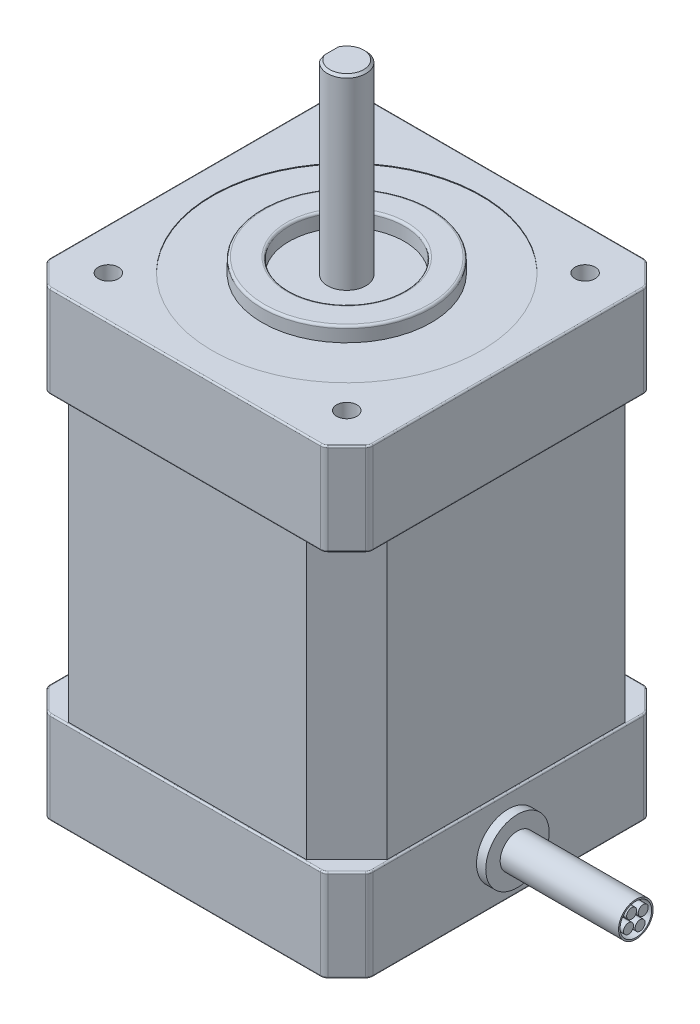
SolidWorks part; units mm, degrees
ref_plane "前视基准面" through (0, 0, 0) normal (0, 0, 1) x (1, 0, 0)
ref_plane "上视基准面" through (0, 0, 0) normal (0, 1, 0) x (1, 0, 0)
ref_plane "右视基准面" through (0, 0, 0) normal (1, 0, 0) x (0, 0, -1)
sketch "草图13" plane through (0, 0, 0) normal (0, 0, 1) x (1, 0, 0)
  line L0 (0, 0) -> (0, 60) construction
  dimension "L" = 60
sketch "草图1" plane through (0, 0, 0) normal (0, 1, 0) x (1, 0, 0)
  line L0 (0, 21) -> (0, -21) construction
  line L1 (-21, 21) -> (21, 21)
  line L2 (-21, 21) -> (-21, -21)
  line L3 (-21, -21) -> (21, -21)
  line L4 (21, 21) -> (21, -21)
  line L5 (-21, 0) -> (21, 0) construction
  dimension "D2" = 21
  dimension "W2" = 42
  dimension "D4" = 21
extrude "凸台-拉伸1" add sketch "草图1" along normal blind 60
chamfer "倒角3" distance 3 angle 45 4 edges at (21, 30, -21) (21, 30, 21) (-21, 30, 21) (-21, 30, -21)
sketch "草图2" plane through (0, 60, 0) normal (0, 1, 0) x (1, 0, 0)
  circle A0 centre (0, 0) radius 11
  dimension "E6" = 22
extrude "凸台-拉伸2" add sketch "草图2" along normal blind 1.8
ref_plane "基准面1" through (0, 12, 0) normal (0, -1, 0) x (1, 0, 0)
sketch "草图3" plane through (0, 60, 0) normal (0, 1, 0) x (1, 0, 0)
  line L0 (-2, 1.5) -> (-2, -1.5) construction
  circle A0 centre (0, 0) radius 2.5
  point P3 (2.5, 0)
  dimension "D1" = 4.5
  dimension "E4" = 5
extrude "凸台-拉伸3" add sketch "草图3" along normal blind 24
sketch "草图4" plane through (0, 12, 0) normal (0, -1, 0) x (1, 0, 0)
  line L0 (15.4716, 20.7) -> (-15.4716, 20.7)
  line L1 (-15.4716, 20.7) -> (-20.7, 15.4716)
  line L2 (-20.7, 15.4716) -> (-20.7, -15.4716)
  line L3 (-20.7, -15.4716) -> (-15.4716, -20.7)
  line L4 (-15.4716, -20.7) -> (15.4716, -20.7)
  line L5 (15.4716, -20.7) -> (20.7, -15.4716)
  line L6 (20.7, -15.4716) -> (20.7, 15.4716)
  line L7 (20.7, 15.4716) -> (15.4716, 20.7)
  line L8 (18, -21) -> (-18, -21) construction
  line L9 (-21, -18) -> (-21, 18) construction
  line L10 (21, 18) -> (21, -18) construction
  line L11 (-18, 21) -> (18, 21) construction
  line L15 (-18, 21) -> (-21, 18) construction
  line L21 (0, -21) -> (0, 21) construction
  line L22 (0, -21) -> (0, 21) construction
  line L23 (-21, 0) -> (21, 0) construction
  dimension "D1" = 0.3
  dimension "D2" = 0.3
  dimension "D3" = 0.3
  dimension "D4" = 0.3
  dimension "D5" = 2
extrude "切除-拉伸1" cut sketch "草图4" against normal blind 36 flip side to cut
fillet "圆角2" radius 1 16 edges at (21, 6, 18) (18, 6, 21) (-18, 6, 21) (-21, 6, 18) (21, 6, -18) (18, 6, -21) (-18, 6, -21) (-21, 6, -18) (-18, 54, -21) (-21, 54, -18) (21, 54, -18) (18, 54, -21) (21, 54, 18) (18, 54, 21) (-18, 54, 21) (-21, 54, 18)
fillet "圆角3" radius 0.2 64 edges at (-21, 48, 0) (-20.9239, 48, 17.9685) (0, 48, 21) (-17.9685, 48, 20.9239) (0, 12, 21) (17.9685, 12, 20.9239) (21, 12, 0) (20.9239, 12, 17.9685) (17.9685, 48, 20.9239) (21, 48, 0) (20.9239, 48, 17.9685) (-21, 12, 0) (-20.9239, 12, 17.9685) (-17.9685, 12, 20.9239) (0, 12, -21) (-17.9685, 12, -20.9239) (-20.9239, 12, -17.9685) (0, 48, -21) (-17.9685, 48, -20.9239) (-20.9239, 48, -17.9685) (-20.9239, 60, -17.9685) (-19.5, 60, -19.5) (-17.9685, 60, -20.9239) (0, 60, -21) (17.9685, 60, -20.9239) (19.5, 60, -19.5) (20.9239, 60, -17.9685) (21, 60, 0) (20.9239, 60, 17.9685) (19.5, 60, 19.5) (17.9685, 60, 20.9239) (0, 60, 21) (-17.9685, 60, 20.9239) (-20.9239, 60, 17.9685) (-20.9239, 0, -17.9685) (-21, 0, 0) (-20.9239, 0, 17.9685) (-19.5, 0, 19.5) (-17.9685, 0, 20.9239) (0, 0, 21) (17.9685, 0, 20.9239) (19.5, 0, 19.5) (20.9239, 0, 17.9685) (21, 0, 0) (20.9239, 0, -17.9685) (19.5, 0, -19.5) (17.9685, 0, -20.9239) (0, 0, -21) (-17.9685, 0, -20.9239) (-19.5, 60, 19.5) (-19.5, 48, 19.5) (19.5, 12, 19.5) (19.5, 48, 19.5) (-19.5, 12, 19.5) (-19.5, 12, -19.5) (-19.5, 48, -19.5) (-21, 60, 0) (-19.5, 0, -19.5) (17.9685, 12, -20.9239) (19.5, 12, -19.5) (20.9239, 12, -17.9685) (17.9685, 48, -20.9239) (19.5, 48, -19.5) (20.9239, 48, -17.9685)
sketch "草图14" plane through (0, 84, 0) normal (0, 1, 0) x (1, 0, 0)
  line L0 (-2, 1.5) -> (-2, -1.5) construction
  line L1 (-2, 1.5) -> (-2, -1.5)
  circle A1 centre (0, 0) radius 2.5 construction
  arc A2 (-2, 1.5) -> (-2, -1.5) centre (0, 0) ccw
extrude "切除-拉伸5" cut sketch "草图14" against normal blind 15
chamfer "倒角5" distance 0.3 angle 45 1 edges at (2.5, 84, 0)
chamfer "倒角4" distance 0.5 angle 45 1 edges at (-2, 69, 0)
chamfer "倒角6" [suppressed] distance 1 angle 45
sketch "草图6" plane through (0, 60, 0) normal (0, 1, 0) x (1, 0, 0)
  line L0 (0, 21) -> (0, -21) construction
  line L3 (-21, 0) -> (21, 0) construction
  line L7 (-21, -21) -> (21, -21) construction
  circle A0 centre (-15.5, 15.5) radius 1.3105
  circle A1 centre (15.5, 15.5) radius 1.3105
  circle A2 centre (15.5, -15.5) radius 1.3105
  circle A3 centre (-15.5, -15.5) radius 1.3105
  dimension "D1" = 31
  dimension "E2" = 2.621
  dimension "E1" = 15.5
extrude "切除-拉伸2" cut sketch "草图6" against normal blind 4.5
cosmetic thread "装饰螺纹线1" parameters "D2"=3
cosmetic thread "装饰螺纹线2" parameters "D2"=3
cosmetic thread "装饰螺纹线3" parameters "D2"=3
cosmetic thread "装饰螺纹线4" parameters "D2"=3
sketch "草图7" plane through (0, 61.8, 0) normal (0, 1, 0) x (1, 0, 0)
  circle A0 centre (0, 0) radius 7.5
  circle A1 centre (0, 0) radius 2.5
  dimension "D1" = 15
  dimension "D2" = 5
extrude "切除-拉伸3" cut sketch "草图7" against normal blind 2
sketch "草图8" plane through (21, 0, 0) normal (1, 0, 0) x (0, 0, -1)
  line L0 (0, 12) -> (0, 0) construction
  line L2 (-15.1716, 12) -> (-18, 12) construction
  circle A0 centre (0, 6) radius 4.125
  dimension "D1" = 8.25
extrude "凸台-拉伸5" add sketch "草图8" along normal blind 1.2
sketch "草图9" plane through (22.2, 0, 0) normal (1, 0, 0) x (0, 0, -1)
  circle A0 centre (0, 6) radius 2.25
  circle A1 centre (0, 6) radius 2.05
  circle A2 centre (0, 6) radius 4.125 construction
  dimension "D1" = 4.5
  dimension "D2" = 0.2
extrude "凸台-拉伸6" add sketch "草图9" along normal blind 15.4
sketch "草图10" plane through (22.2, 0, 0) normal (1, 0, 0) x (0, 0, -1)
  line L0 (0, 6) -> (-0.9526, 6.55) construction
  line L1 (0, 6) -> (0.9526, 6.55) construction
  line L2 (0, 6) -> (0, 4.9) construction
  circle A0 centre (-0.9526, 6.55) radius 0.65 construction
  circle A1 centre (0.9526, 6.55) radius 0.65
  circle A2 centre (0, 4.9) radius 0.65 construction
  circle A5 centre (0, 6) radius 1.1 construction
  dimension "D1" = 120
  dimension "D2" = 2.2
  dimension "D3" = 1.3
  dimension "D4" = 120
extrude "凸台-拉伸8" add sketch "草图10" along normal blind 15.4 contours A0 | A2 | A1
sketch "草图15" plane through (0, 60, 0) normal (0, 1, 0) x (1, 0, 0)
  circle A0 centre (0, 0) radius 17.5
  circle A1 centre (0, 0) radius 11 construction
  circle A2 centre (0, 0) radius 11
  dimension "D1" = 35
extrude "切除-拉伸6" cut sketch "草图15" against normal blind 0.1
fillet "圆角4" radius 0.3 2 edges at (0, 61.8, 7.5) (0, 61.8, 11)
pattern_circular "阵列(圆周)3" count 4 over 360 about axis through (0, 6, 0) along (1, 0, 0) of "凸台-拉伸8"
sketch "草图16" [suppressed] plane through (0, 0, -20.85) normal (0, 0, -1) x (-1, 0, 0)
  line L0 (0, 36.8) -> (0, 9.2) construction
  line L1 (15.6216, 36.8) -> (-15.6216, 36.8) construction
  line L2 (15.6216, 9.2) -> (-15.6216, 9.2) construction
  line L4 (-12.5, 7.2) -> (12.5, 7.2)
  line L5 (-12.5, 7.2) -> (-12.5, 38.8)
  line L6 (-12.5, 38.8) -> (12.5, 38.8)
  line L7 (12.5, 7.2) -> (12.5, 38.8)
  line L8 (-12.5, 7.2) -> (12.5, 38.8) construction
  line L9 (-12.5, 38.8) -> (12.5, 7.2) construction
  point P6 (0, 23)
  dimension "D1" = 2
  dimension "D2" = 25
extrude "切除-拉伸9" [suppressed] cut sketch "草图16" along normal blind 0.3
sketch "草图17" [suppressed] plane through (0, 0, 20.85) normal (0, 0, 1) x (1, 0, 0)
  line L4 (-12.5, 7.2) -> (12.5, 7.2)
  line L5 (-12.5, 38.8) -> (-12.5, 7.2)
  line L6 (12.5, 38.8) -> (-12.5, 38.8)
  line L7 (12.5, 7.2) -> (12.5, 38.8)
  line L8 (-12.5, 7.2) -> (12.5, 7.2)
  line L9 (-12.5, 38.8) -> (-12.5, 7.2)
  line L10 (12.5, 38.8) -> (-12.5, 38.8)
  line L11 (12.5, 7.2) -> (12.5, 38.8)
  dimension "D1" = 0
extrude "切除-拉伸10" [suppressed] cut sketch "草图17" along normal up to surface (0.3 mm away)
sketch "草图18" [suppressed] plane through (20.85, 0, 0) normal (1, 0, 0) x (0, 0, -1)
  line L0 (0, 9.2) -> (0, 36.8) construction
  line L1 (15.6216, 9.2) -> (-15.6216, 9.2) construction
  line L2 (15.6216, 36.8) -> (-15.6216, 36.8) construction
  line L4 (-12.5, 8.2) -> (12.5, 8.2)
  line L5 (-12.5, 8.2) -> (-12.5, 37.8)
  line L6 (-12.5, 37.8) -> (12.5, 37.8)
  line L7 (12.5, 8.2) -> (12.5, 37.8)
  line L8 (-12.5, 8.2) -> (12.5, 37.8) construction
  line L9 (-12.5, 37.8) -> (12.5, 8.2) construction
  point P6 (0, 23)
  dimension "D1" = 1
  dimension "D2" = 25
extrude "切除-拉伸11" [suppressed] cut sketch "草图18" along normal up to surface (0.3 mm away)
sketch "草图19" [suppressed] plane through (-20.85, 0, 0) normal (-1, 0, 0) x (0, 0, 1)
  line L4 (-12.5, 8.2) -> (12.5, 8.2)
  line L5 (-12.5, 37.8) -> (-12.5, 8.2)
  line L6 (12.5, 37.8) -> (-12.5, 37.8)
  line L7 (12.5, 8.2) -> (12.5, 37.8)
  line L8 (-12.5, 8.2) -> (12.5, 8.2)
  line L9 (-12.5, 37.8) -> (-12.5, 8.2)
  line L10 (12.5, 37.8) -> (-12.5, 37.8)
  line L11 (12.5, 8.2) -> (12.5, 37.8)
  dimension "D1" = 0
extrude "切除-拉伸12" [suppressed] cut sketch "草图19" along normal up to surface (0.3 mm away)
